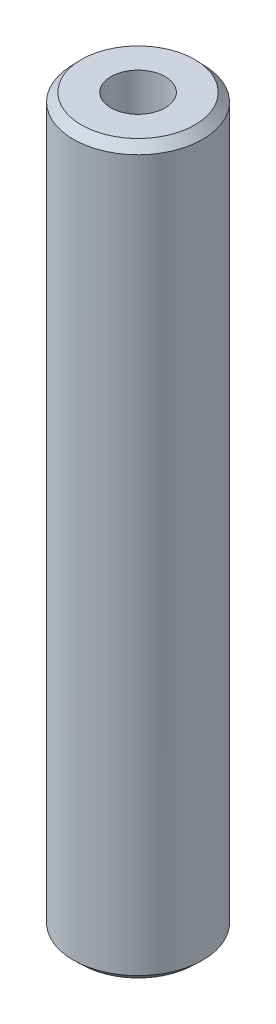
SolidWorks part; units mm, degrees
ref_plane "Front Plane" through (0, 0, 0) normal (0, 0, 1) x (1, 0, 0)
ref_plane "Top Plane" through (0, 0, 0) normal (0, 1, 0) x (1, 0, 0)
ref_plane "Right Plane" through (0, 0, 0) normal (1, 0, 0) x (0, 0, -1)
sketch "Sketch1" plane through (0, 0, 0) normal (0, 1, 0) x (1, 0, 0)
  circle A0 centre (0, 0) radius 10
  dimension "SHAFT_OD" = 20
extrude "Boss-Extrude1" add sketch "Sketch1" along normal blind 112.3857
sketch "Sketch2" plane through (0, 0, 0) normal (0, 1, 0) x (1, 0, 0)
  circle A0 centre (0, 0) radius 4.1895
  dimension "BORE_D" = 8.379
extrude "Cut-Extrude1" cut sketch "Sketch2" along normal through all
chamfer "Chamfer1" distance 1.3032 angle 43.508 2 edges at (0, 112.3857, 10) (0, 0, 10) first distance on face at (0, 112.3857, 10) first distance on face at (0, 0, 4.1895)
